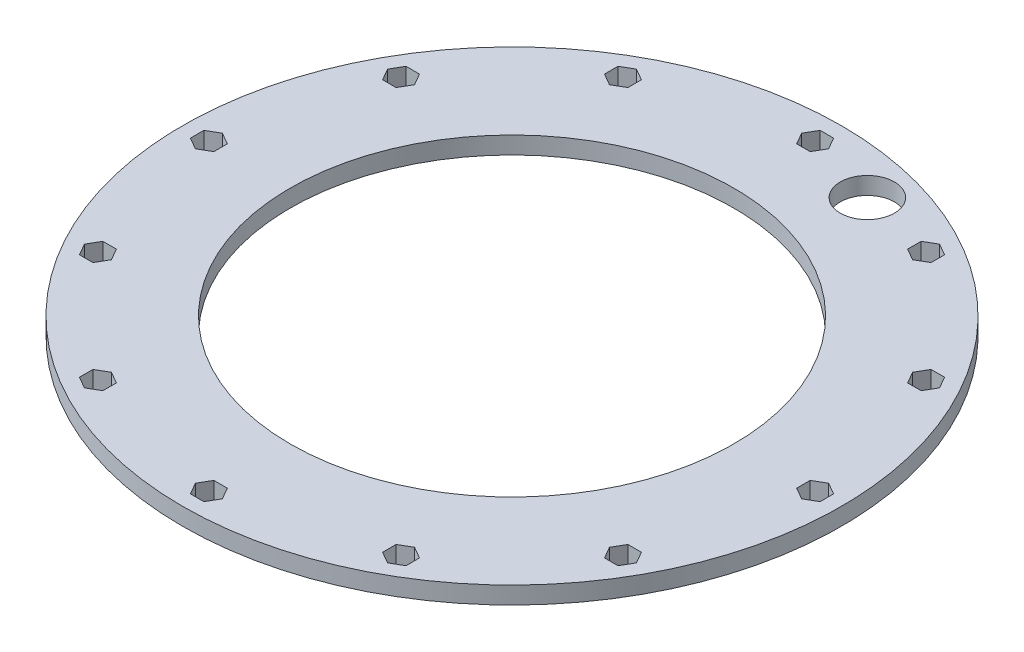
SolidWorks part; units mm, degrees
material "1060 Alloy"
ref_plane "Ebene vorne" through (0, 0, 0) normal (0, 0, 1) x (1, 0, 0)
ref_plane "Ebene oben" through (0, 0, 0) normal (0, 1, 0) x (1, 0, 0)
ref_plane "Ebene rechts" through (0, 0, 0) normal (1, 0, 0) x (0, 0, -1)
sketch "Sketch1" plane through (0, 0, 0) normal (0, 1, 0) x (1, 0, 0)
  circle A0 centre (0, 0) radius 51.2
  circle A1 centre (0, 0) radius 76.1
  dimension "D1" = 152.2
  dimension "D2" = 102.4
extrude "Boss-Extrude1" add sketch "Sketch1" along normal blind 4
sketch "Sketch2" plane through (0, 4, 0) normal (0, 1, 0) x (1, 0, 0)
  line L0 (37.7, 59.0629) -> (37.7, 62.1806)
  line L1 (3.1177, 70) -> (1.5588, 72.7)
  line L2 (1.5588, 72.7) -> (-1.5588, 72.7)
  line L3 (-1.5588, 72.7) -> (-3.1177, 70)
  line L4 (-3.1177, 70) -> (-1.5588, 67.3)
  line L5 (-1.5588, 67.3) -> (1.5588, 67.3)
  line L6 (1.5588, 67.3) -> (3.1177, 70)
  line L7 (37.7, 62.1806) -> (35, 63.7395)
  line L8 (35, 63.7395) -> (32.3, 62.1806)
  line L9 (32.3, 62.1806) -> (32.3, 59.0629)
  line L10 (32.3, 59.0629) -> (35, 57.5041)
  line L11 (35, 57.5041) -> (37.7, 59.0629)
  line L12 (62.1806, 32.3) -> (63.7395, 35)
  line L13 (63.7395, 35) -> (62.1806, 37.7)
  line L14 (62.1806, 37.7) -> (59.0629, 37.7)
  line L15 (59.0629, 37.7) -> (57.5041, 35)
  line L16 (57.5041, 35) -> (59.0629, 32.3)
  line L17 (59.0629, 32.3) -> (62.1806, 32.3)
  line L18 (70, -3.1177) -> (72.7, -1.5588)
  line L19 (72.7, -1.5588) -> (72.7, 1.5588)
  line L20 (72.7, 1.5588) -> (70, 3.1177)
  line L21 (70, 3.1177) -> (67.3, 1.5588)
  line L22 (67.3, 1.5588) -> (67.3, -1.5588)
  line L23 (67.3, -1.5588) -> (70, -3.1177)
  line L24 (59.0629, -37.7) -> (62.1806, -37.7)
  line L25 (62.1806, -37.7) -> (63.7395, -35)
  line L26 (63.7395, -35) -> (62.1806, -32.3)
  line L27 (62.1806, -32.3) -> (59.0629, -32.3)
  line L28 (59.0629, -32.3) -> (57.5041, -35)
  line L29 (57.5041, -35) -> (59.0629, -37.7)
  line L30 (32.3, -62.1806) -> (35, -63.7395)
  line L31 (35, -63.7395) -> (37.7, -62.1806)
  line L32 (37.7, -62.1806) -> (37.7, -59.0629)
  line L33 (37.7, -59.0629) -> (35, -57.5041)
  line L34 (35, -57.5041) -> (32.3, -59.0629)
  line L35 (32.3, -59.0629) -> (32.3, -62.1806)
  line L36 (-3.1177, -70) -> (-1.5588, -72.7)
  line L37 (-1.5588, -72.7) -> (1.5588, -72.7)
  line L38 (1.5588, -72.7) -> (3.1177, -70)
  line L39 (3.1177, -70) -> (1.5588, -67.3)
  line L40 (1.5588, -67.3) -> (-1.5588, -67.3)
  line L41 (-1.5588, -67.3) -> (-3.1177, -70)
  line L42 (-37.7, -59.0629) -> (-37.7, -62.1806)
  line L43 (-37.7, -62.1806) -> (-35, -63.7395)
  line L44 (-35, -63.7395) -> (-32.3, -62.1806)
  line L45 (-32.3, -62.1806) -> (-32.3, -59.0629)
  line L46 (-32.3, -59.0629) -> (-35, -57.5041)
  line L47 (-35, -57.5041) -> (-37.7, -59.0629)
  line L48 (-62.1806, -32.3) -> (-63.7395, -35)
  line L49 (-63.7395, -35) -> (-62.1806, -37.7)
  line L50 (-62.1806, -37.7) -> (-59.0629, -37.7)
  line L51 (-59.0629, -37.7) -> (-57.5041, -35)
  line L52 (-57.5041, -35) -> (-59.0629, -32.3)
  line L53 (-59.0629, -32.3) -> (-62.1806, -32.3)
  line L54 (-70, 3.1177) -> (-72.7, 1.5588)
  line L55 (-72.7, 1.5588) -> (-72.7, -1.5588)
  line L56 (-72.7, -1.5588) -> (-70, -3.1177)
  line L57 (-70, -3.1177) -> (-67.3, -1.5588)
  line L58 (-67.3, -1.5588) -> (-67.3, 1.5588)
  line L59 (-67.3, 1.5588) -> (-70, 3.1177)
  line L60 (-59.0629, 37.7) -> (-62.1806, 37.7)
  line L61 (-62.1806, 37.7) -> (-63.7395, 35)
  line L62 (-63.7395, 35) -> (-62.1806, 32.3)
  line L63 (-62.1806, 32.3) -> (-59.0629, 32.3)
  line L64 (-59.0629, 32.3) -> (-57.5041, 35)
  line L65 (-57.5041, 35) -> (-59.0629, 37.7)
  line L66 (-32.3, 62.1806) -> (-35, 63.7395)
  line L67 (-35, 63.7395) -> (-37.7, 62.1806)
  line L68 (-37.7, 62.1806) -> (-37.7, 59.0629)
  line L69 (-37.7, 59.0629) -> (-35, 57.5041)
  line L70 (-35, 57.5041) -> (-32.3, 59.0629)
  line L71 (-32.3, 59.0629) -> (-32.3, 62.1806)
  circle A0 centre (35, 60.6218) radius 2.7 construction
  circle A1 centre (60.6218, 35) radius 2.7 construction
  circle A2 centre (70, 0) radius 2.7 construction
  circle A3 centre (60.6218, -35) radius 2.7 construction
  circle A4 centre (35, -60.6218) radius 2.7 construction
  circle A5 centre (0, -70) radius 2.7 construction
  circle A7 centre (-35, -60.6218) radius 2.7 construction
  circle A8 centre (-60.6218, -35) radius 2.7 construction
  circle A9 centre (-70, 0) radius 2.7 construction
  circle A10 centre (-60.6218, 35) radius 2.7 construction
  circle A11 centre (-35, 60.6218) radius 2.7 construction
  circle A12 centre (0, 70) radius 2.7 construction
  point P28 (0, 0)
  point P103 (0, 0)
  dimension "D1" = 5.4
  dimension "D2" = 70
  dimension "D3" = 12
extrude "Cut-Extrude1" cut sketch "Sketch2" against normal through all
sketch "Sketch3" plane through (0, 4, 0) normal (0, 1, 0) x (1, 0, 0)
  line L0 (17.3409, 64.717) -> (0, 0) construction
  line L1 (0, 0) -> (0, 80.521) construction
  circle A0 centre (17.3409, 64.717) radius 6.25
  dimension "D1" = 12.5
  dimension "D3" = 15
  dimension "D2" = 67
extrude "Cut-Extrude2" cut sketch "Sketch3" against normal blind 10
